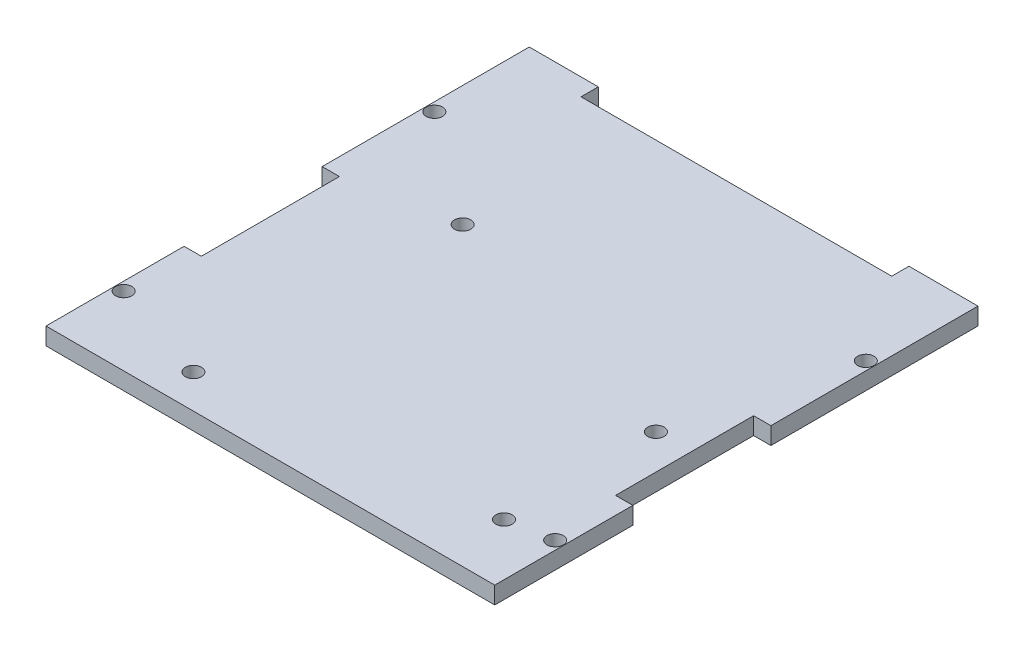
SolidWorks part; units mm, degrees
ref_plane "Front Plane" through (0, 0, 0) normal (0, 0, 1) x (1, 0, 0)
ref_plane "Top Plane" through (0, 0, 0) normal (0, 1, 0) x (1, 0, 0)
ref_plane "Right Plane" through (0, 0, 0) normal (1, 0, 0) x (0, 0, -1)
sketch "Sketch1" plane through (0, 0, 0) normal (0, 1, 0) x (1, 0, 0)
  line L0 (-41.275, 0) -> (-36.3683, -11.7139)
  line L1 (3.175, 88.9) -> (3.175, 85.725) construction
  line L2 (28.575, 85.725) -> (3.175, 85.725)
  line L3 (-41.275, 88.9) -> (-28.575, 88.9)
  line L4 (28.575, 88.9) -> (28.575, 85.725)
  line L5 (41.275, 50.8) -> (41.275, 88.9)
  line L6 (-41.275, 0) -> (-38.1, 0) construction
  line L7 (-41.275, 50.8) -> (-38.1, 50.8)
  line L8 (0, 63.5) -> (0, -63.5) construction
  line L9 (38.1, 50.8) -> (38.1, 25.4)
  line L10 (-38.1, 50.8) -> (-38.1, 25.4)
  line L11 (-41.275, 50.8) -> (-41.275, 88.9)
  line L12 (41.275, 50.8) -> (38.1, 50.8)
  line L13 (-28.575, 88.9) -> (-28.575, 85.725)
  line L14 (-28.575, 85.725) -> (-3.175, 85.725)
  line L15 (-3.175, 88.9) -> (-3.175, 85.725) construction
  line L16 (41.275, 88.9) -> (28.575, 88.9)
  line L17 (-41.275, 0) -> (41.275, 0) construction
  line L18 (-38.1, 0) -> (-38.1, 25.4) construction
  line L19 (-38.1, 25.4) -> (-41.275, 25.4)
  line L20 (-3.175, 88.9) -> (3.175, 88.9) construction
  line L21 (-41.275, 0) -> (-41.275, 25.4)
  line L22 (38.1, 25.4) -> (41.275, 25.4)
  line L23 (-38.1, 0) -> (-33.467, -10.4244) construction
  line L24 (41.275, 0) -> (41.275, 25.4)
  line L25 (33.467, -10.4244) -> (38.1, 0) construction
  line L26 (-36.3683, -11.7139) -> (-33.467, -10.4244) construction
  line L27 (41.275, 0) -> (36.3683, -11.7139)
  line L28 (36.3683, -11.7139) -> (33.467, -10.4244) construction
  line L29 (-17.858, -45.5446) -> (-12.7, -57.15) construction
  line L30 (-12.7, -57.15) -> (-15.6014, -58.4395) construction
  line L31 (-17.858, -45.5446) -> (-20.7593, -46.8341)
  line L32 (-15.6014, -58.4395) -> (-20.7593, -46.8341)
  line L33 (12.7, -57.15) -> (17.858, -45.5446) construction
  line L34 (-33.467, -10.4244) -> (-17.858, -45.5446)
  line L35 (-12.7, -57.15) -> (12.7, -57.15) construction
  line L36 (17.858, -45.5446) -> (33.467, -10.4244)
  line L37 (-3.175, 85.725) -> (3.175, 85.725)
  line L38 (41.275, 69.85) -> (-41.275, 69.85) construction
  line L39 (12.7, -57.15) -> (15.6014, -58.4395) construction
  line L40 (17.858, -45.5446) -> (20.7593, -46.8341)
  line L41 (15.6014, -58.4395) -> (20.7593, -46.8341)
  line L42 (38.1, 0) -> (38.1, 25.4) construction
  line L43 (-15.6014, -58.4395) -> (-12.7, -60.325)
  line L44 (-5.08, -57.15) -> (-12.7, -57.15) construction
  line L45 (-5.08, -57.15) -> (-5.08, -60.325)
  line L46 (-5.08, -60.325) -> (-12.7, -60.325)
  line L47 (-12.7, -57.15) -> (-12.7, -60.325) construction
  line L48 (5.08, -57.15) -> (12.7, -57.15) construction
  line L49 (5.08, -57.15) -> (5.08, -60.325)
  line L50 (5.08, -60.325) -> (12.7, -60.325)
  line L51 (12.7, -57.15) -> (12.7, -60.325) construction
  line L52 (15.6014, -58.4395) -> (12.7, -60.325)
  line L53 (-5.08, -57.15) -> (5.08, -57.15)
  line L54 (33.467, -10.4244) -> (36.3683, -11.7139)
  line L55 (-33.467, -10.4244) -> (-36.3683, -11.7139)
  point P0 (0, 0)
  point P1 (0, -57.15)
  dimension "D1" = 25.4
  dimension "D2" = 57.15
  dimension "D3" = 3.175
  dimension "D4" = 82.55
  dimension "D5" = 3.175
  dimension "D6" = 12.7
  dimension "D7" = 25.4
  dimension "D8" = 38.1
  dimension "D9" = 50.8
  dimension "D10" = 25.4
  dimension "D11" = 12.7
  dimension "D12" = 12.7
  dimension "D13" = 10.16
extrude "Boss-Extrude1" add sketch "Sketch1" along normal blind 3.175
sketch "Sketch2" plane through (0, 0, 0) normal (0, -1, 0) x (-1, 0, 0)
  line L0 (39.6875, 50.8) -> (39.6875, 88.9) construction
  line L1 (41.275, 50.8) -> (38.1, 50.8) construction
  line L2 (28.575, 88.9) -> (41.275, 88.9) construction
  line L3 (0, 85.725) -> (0, -57.15) construction
  line L6 (-5.08, -58.7375) -> (-15.1428, -58.7375) construction
  line L7 (5.08, -57.15) -> (-5.08, -57.15) construction
  line L10 (28.575, 88.9) -> (41.275, 88.9) construction
  line L11 (39.6875, 25.4) -> (39.6875, -3.7899) construction
  line L12 (38.1, 25.4) -> (41.275, 25.4) construction
  line L14 (-28.575, 85.725) -> (28.575, 85.725) construction
  line L15 (41.275, 0) -> (36.3683, -11.7139) construction
  line L18 (34.9176, -11.0691) -> (41.275, 3.235) construction
  line L23 (36.3683, -11.7139) -> (33.467, -10.4244) construction
  line L24 (41.275, 25.4) -> (41.275, 0) construction
  line L25 (19.3086, -46.1893) -> (13.0261, -60.325) construction
  line L26 (17.858, -45.5446) -> (20.7593, -46.8341) construction
  line L27 (12.7, -60.325) -> (5.08, -60.325) construction
  line L28 (5.08, -58.7375) -> (15.1428, -58.7375) construction
  line L29 (5.08, -60.325) -> (5.08, -57.15) construction
  line L30 (15.6014, -58.4395) -> (12.7, -60.325) construction
  line L31 (-19.3086, -46.1893) -> (-13.0261, -60.325) construction
  line L32 (-34.9176, -11.0691) -> (-41.275, 3.235) construction
  line L33 (-39.6875, 25.4) -> (-39.6875, -3.7899) construction
  line L34 (-39.6875, 50.8) -> (-39.6875, 88.9) construction
  circle A0 centre (39.6875, 69.85) radius 1.5
  circle A1 centre (-8.89, -58.7375) radius 1.5
  circle A2 centre (39.6875, 12.7) radius 1.5
  circle A3 centre (37.4966, -5.2664) radius 1.5
  circle A4 centre (16.7297, -51.992) radius 1.5
  circle A5 centre (8.89, -58.7375) radius 1.5
  circle A6 centre (-16.7297, -51.992) radius 1.5
  circle A7 centre (-37.4966, -5.2664) radius 1.5
  circle A8 centre (-39.6875, 12.7) radius 1.5
  circle A9 centre (-39.6875, 69.85) radius 1.5
  dimension "D1" = 3
  dimension "D4" = 6.35
  dimension "D6" = 3.81
  dimension "D2" = 3
  dimension "D3" = 12.7
  dimension "D5" = 6.35
extrude "Cut-Extrude1" cut sketch "Sketch2" against normal through all
sketch "Sketch4" plane through (0, 3.175, 0) normal (0, 1, 0) x (1, 0, 0)
  circle A0 centre (31.6815, 11.305) radius 1.5
  circle A1 centre (31.6815, 39.245) radius 1.5
  circle A2 centre (-20.3885, 6.225) radius 1.5
  circle A3 centre (-19.1185, 54.485) radius 1.5
  dimension "D1" = 3
  dimension "D2" = 3
  dimension "D3" = 3
  dimension "D4" = 3
extrude "Cut-Extrude3" cut sketch "Sketch4" against normal through all
sketch "Sketch5" plane through (0, 3.175, 0) normal (0, 1, 0) x (1, 0, 0)
  line L0 (-41.275, 25.4) -> (-41.275, 0) construction
  line L1 (41.275, 0) -> (-41.275, 0)
  line L2 (41.275, 0) -> (41.275, -60.325)
  line L3 (41.275, -60.325) -> (-41.275, -60.325)
  line L4 (-41.275, 0) -> (-41.275, -60.325)
  line L5 (-12.7, -60.325) -> (-5.08, -60.325) construction
extrude "Cut-Extrude4" cut sketch "Sketch5" against normal through all
